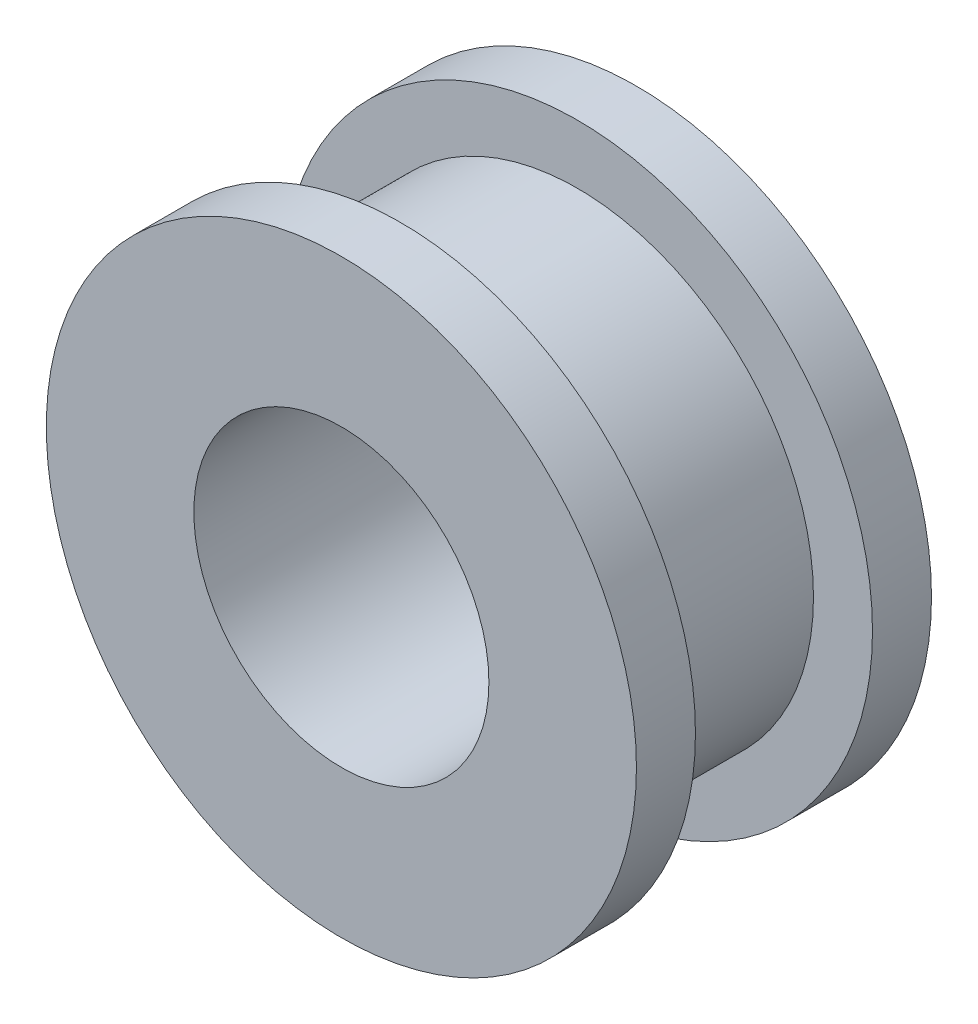
SolidWorks part; units mm, degrees
ref_plane "Front Plane" through (0, 0, 0) normal (0, 0, 1) x (1, 0, 0)
ref_plane "Top Plane" through (0, 0, 0) normal (0, 1, 0) x (1, 0, 0)
ref_plane "Right Plane" through (0, 0, 0) normal (1, 0, 0) x (0, 0, -1)
sketch "Sketch1" plane through (0, 0, 0) normal (0, 0, 1) x (1, 0, 0)
  circle A0 centre (0, 0) radius 2.5
  circle A1 centre (0, 0) radius 5
  circle A2 centre (0, 0) radius 4
  dimension "D1" = 5
  dimension "D2" = 10
  dimension "D3" = 8
extrude "Boss-Extrude1" add sketch "Sketch1" along normal blind 5 contours A2 A0 | A1 A2 region at (-4.8586, 0, 0) region at (-3.8869, 0, 0)
extrude "Cut-Extrude1" cut sketch "Sketch1<3>" along normal blind 3 from offset 1 contours A1 A2 region at (-4.8586, 0, 0)
sketch "Sketch1<3>" plane through (0, 0, 0) normal (0, 0, 1) x (1, 0, 0) same geometry as "Sketch1"
